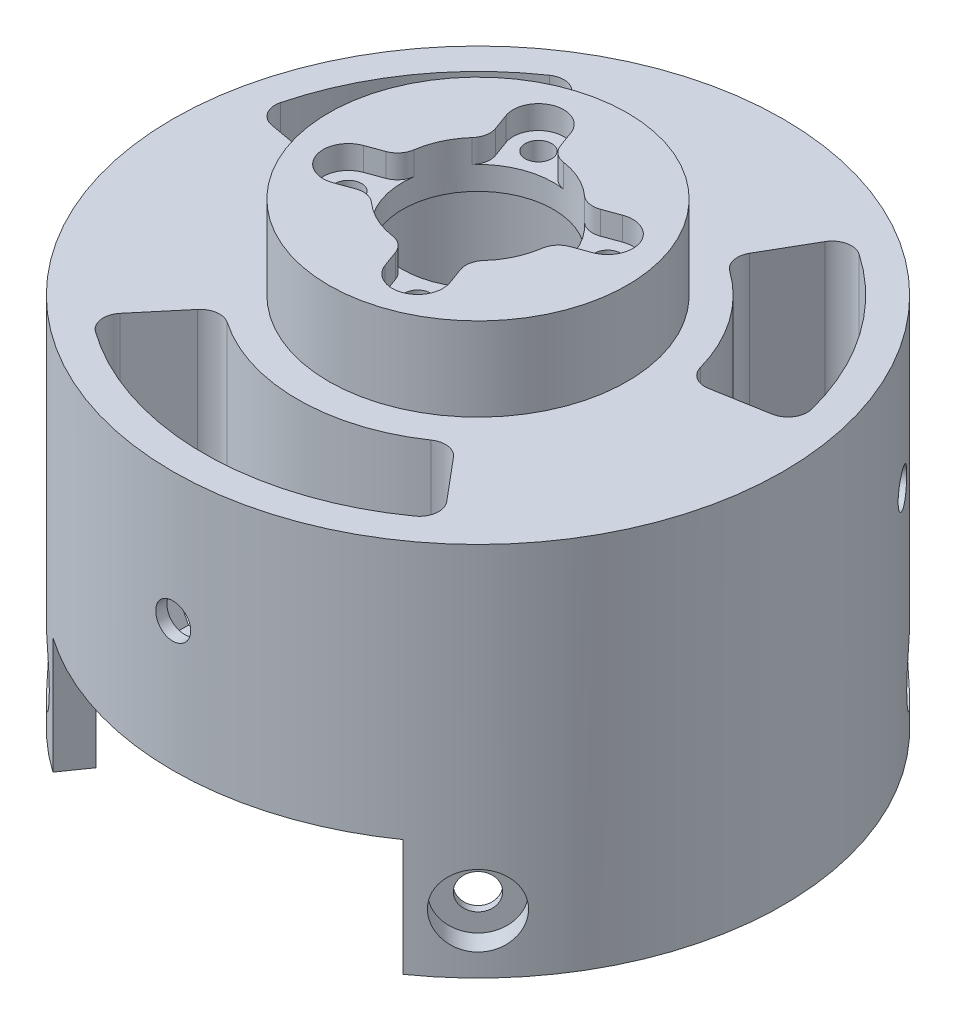
SolidWorks part; units mm, degrees
material "PLA - 3D Printed"
ref_plane "Front Plane" through (0, 0, 0) normal (0, 0, 1) x (1, 0, 0)
ref_plane "Top Plane" through (0, 0, 0) normal (0, 1, 0) x (1, 0, 0)
ref_plane "Right Plane" through (0, 0, 0) normal (1, 0, 0) x (0, 0, -1)
sketch "Sketch1" plane through (0, 0, 0) normal (0, 1, 0) x (1, 0, 0)
  line L0 (-29.85, 23.9174) -> (-29.85, -23.9174)
  line L1 (29.85, 23.9174) -> (29.85, -23.9174)
  line L2 (-29.85, 0) -> (29.85, 0) construction
  arc A0 (-29.85, -23.9174) -> (29.85, -23.9174) centre (0, 0) ccw
  arc A1 (29.85, 23.9174) -> (-29.85, 23.9174) centre (0, 0) ccw
  point P9 (0, 0)
  dimension "D1" = 59.7
  dimension "D2" = 76.5
extrude "Boss-Extrude1" add sketch "Sketch1" along normal blind 44
sketch "Sketch2" plane through (0, 44, 0) normal (0, 1, 0) x (1, 0, 0)
  line L0 (-4.4463, 12.216) -> (0, 0) construction
  line L1 (0, 13) -> (0, 0) construction
  circle A0 centre (0, 0) radius 13
  point P3 (-4.4463, 12.216)
  dimension "D1" = 26
  dimension "D2" = 20
hole_wizard "CBORE for M3 SHCS1" positions "Sketch2" profile "Sketch3" counterbore size "M3" standard "ANSI Metric" end condition through all
sketch "Sketch3" plane through (-4.4463, 44, -12.216) normal (1, 0, 0) x (0, 0, 1)
  line L0 (0, 0) -> (0, 44)
  line L1 (0, 44) -> (1.7, 44)
  line L3 (1.7, 44) -> (1.7, 3)
  line L4 (1.7, 3) -> (3.25, 3)
  line L5 (3.25, 3) -> (3.25, 0)
  line L7 (3.25, 0) -> (0, 0)
  line L11 (0, -6.35) -> (0, 107.95) construction
  dimension "Thru Hole Dia." = 3.4
  dimension "Thru Hole Depth" = 44
  dimension "C'Bore Dia." = 6.5
  dimension "C'Bore Depth" = 3
ref_axis "Axis1" through (0, 44, 0) along (0, -1, 0)
pattern_circular "CirPattern1" count 4 over 360 about axis through (0, 44, 0) along (0, -1, 0) of "CBORE for M3 SHCS1"
sketch "Sketch4" plane through (0, 0, 0) normal (0, -1, 0) x (1, 0, 0)
  circle A0 centre (0, 0) radius 16.2
  dimension "D1" = 32.4
extrude "Cut-Extrude1" cut sketch "Sketch4" against normal blind 38
sketch "Sketch5" plane through (0, 44, 0) normal (0, 1, 0) x (1, 0, 0)
  circle A0 centre (0, 0) radius 9.7
extrude "Cut-Extrude2" cut sketch "Sketch5" against normal through all
ref_plane "Plane1" through (0, 0, -38.25) normal (0, 0, -1) x (-1, 0, 0)
sketch "Sketch7" plane through (0, 0, 0) normal (0, -1, 0) x (1, 0, 0)
  line L5 (29.85, 23.9174) -> (29.85, -23.9174)
  line L6 (-29.85, 23.9174) -> (-29.85, -23.9174)
  arc A0 (-29.85, -23.9174) -> (29.85, -23.9174) centre (0, 0) ccw construction
  arc A1 (29.85, 23.9174) -> (-29.85, 23.9174) centre (0, 0) ccw construction
  arc A2 (-29.85, -23.9174) -> (29.85, -23.9174) centre (0, 0) ccw
  arc A3 (29.85, 23.9174) -> (-29.85, 23.9174) centre (0, 0) ccw
  circle A4 centre (0, 0) radius 42.1622
  dimension "D1" = 84.3245
extrude "Boss-Extrude2" add sketch "Sketch7" against normal up to surface (44 mm away) up to face at (0, 44, 9.7)
sketch "Sketch9" plane through (0, 0, 0) normal (1, 0, 0) x (0, 0, -1)
  line L0 (-42.1622, 0) -> (-38.3127, 44)
  line L1 (-38.3127, 44) -> (-42.1622, 44)
  line L2 (-42.1622, 44) -> (-42.1622, 0) construction
  line L3 (-42.1622, 44) -> (-42.1622, 0)
  line L4 (0, 0) -> (0, 44) construction
  line L5 (42.1622, 44) -> (-42.1622, 44) construction
  dimension "D1" = 5
revolve "Cut-Revolve2" cut sketch "Sketch9" angle 360 about L4
sketch "Sketch10" plane through (0, 0, 0) normal (1, 0, 0) x (0, 0, -1)
  line L0 (-19.2, 44) -> (-19.2, 33.2871)
  line L1 (38.3127, 44) -> (-38.3127, 44) construction
  line L2 (-19.2, 33.2871) -> (-39.25, 33.2871)
  line L3 (-38.3127, 44) -> (-42.1622, 0) construction
  line L4 (-39.25, 33.2871) -> (-38.3127, 44)
  line L5 (-38.3127, 44) -> (-19.2, 44)
  line L6 (0, 0) -> (0, 44) construction
  line L10 (-42.1622, 0) -> (42.1622, 0) construction
  line L11 (-16.2, 0) -> (16.2, 0) construction
  line L12 (-16.2, 0) -> (16.2, 0) construction
  line L13 (38.3127, 44) -> (-38.3127, 44) construction
  dimension "D1" = 10.7129
  dimension "D2" = 33.2871
  dimension "D3" = 3
revolve "Cut-Revolve3" cut sketch "Sketch10" angle 360 about L6
sketch "Sketch13" plane through (0, 33.2871, 0) normal (0, 1, 0) x (1, 0, 0)
  line L0 (0, -35.25) -> (0, -39.25) construction
  circle A0 centre (0, 0) radius 35.25
  circle A1 centre (0, 0) radius 19.2 construction
  circle A2 centre (0, 0) radius 19.2
  circle A3 centre (0, 0) radius 39.25 construction
  dimension "D1" = 4
extrude "Cut-Extrude3" cut sketch "Sketch13" against normal through all both and the other way through all
sketch "Sketch16" plane through (0, 0, 0) normal (0, -1, 0) x (1, 0, 0)
  line L0 (0, -35.25) -> (0, -19.2) construction
  line L1 (-17.625, -30.5274) -> (-9.6, -16.6277)
  line L2 (17.625, -30.5274) -> (9.6, -16.6277)
  line L3 (-34.7145, -6.1211) -> (-18.9083, -3.334)
  line L4 (-22.6583, 27.0031) -> (-12.3415, 14.7081)
  line L5 (22.6583, 27.0031) -> (12.3415, 14.7081)
  line L6 (34.7145, -6.1211) -> (18.9083, -3.334)
  line L7 (0, 0) -> (-33.1242, 12.0562) construction
  circle A1 centre (0, 0) radius 35.25 construction
  circle A2 centre (0, 0) radius 19.2 construction
  arc A3 (-9.6, -16.6277) -> (9.6, -16.6277) centre (0, 0) ccw
  arc A4 (-17.625, -30.5274) -> (17.625, -30.5274) centre (0, 0) ccw
  arc A5 (-22.6583, 27.0031) -> (-34.7145, -6.1211) centre (0, 0) ccw
  arc A6 (-12.3415, 14.7081) -> (-18.9083, -3.334) centre (0, 0) ccw
  arc A7 (22.6583, 27.0031) -> (34.7145, -6.1211) centre (0, 0) cw
  arc A8 (12.3415, 14.7081) -> (18.9083, -3.334) centre (0, 0) cw
  point P19 (0, 0)
  dimension "D1" = 16.05
  dimension "D3" = 60
  dimension "D4" = 110
  dimension "D2" = 2
extrude "Boss-Extrude4" add sketch "Sketch16" against normal up to surface (33.2871 mm away) up to face at (0, 33.2871, 35.25)
sketch "Sketch17" plane through (0, 33.2871, 0) normal (0, 1, 0) x (1, 0, 0)
  line L0 (0, -19.2) -> (0, -23.2) construction
  circle A0 centre (0, 0) radius 23.2
  circle A1 centre (0, 0) radius 19.2 construction
  circle A2 centre (0, 0) radius 19.2
  dimension "D1" = 4
extrude "Boss-Extrude5" add sketch "Sketch17" against normal up to surface (33.2871 mm away) up to face at (-21.2567, 0, -14.8841)
fillet "Fillet2" radius 2.5 12 edges at (-14.9127, 16.6435, 17.7722) (-22.6583, 16.6435, 27.0031) (22.6583, 16.6435, 27.0031) (14.9127, 16.6435, 17.7722) (-17.625, 16.6435, -30.5274) (-34.7145, 16.6435, -6.1211) (-22.8475, 16.6435, -4.0286) (-11.6, 16.6435, -20.0918) (34.7145, 16.6435, -6.1211) (17.625, 16.6435, -30.5274) (11.6, 16.6435, -20.0918) (22.8475, 16.6435, -4.0286)
ref_plane "Plane2" through (0, 16.6435, 0) normal (0, -1, 0) x (-1, 0, 0)
sketch "Sketch18" plane through (0, 16.6435, 0) normal (0, -1, 0) x (-1, 0, 0)
  line L0 (0, 0) -> (28.8751, 20.2186) construction
  line L1 (0, 0) -> (-28.8751, 20.2186) construction
  line L2 (0, 0) -> (0, -35.25) construction
  line L3 (0, 0) -> (-10.7822, -33.5605) construction
  line L4 (0, 0) -> (10.7822, -33.5605) construction
  arc A0 (34.1459, 8.7532) -> (19.9039, 29.0929) centre (0, 0) ccw construction
  arc A1 (-19.9039, 29.0929) -> (-34.1459, 8.7532) centre (0, 0) ccw construction
  arc A2 (-20.5308, -28.6539) -> (20.5308, -28.6539) centre (0, 0) ccw construction
  arc A3 (-20.5308, -28.6539) -> (0, -35.25) centre (0, 0) ccw construction
  arc A4 (0, -35.25) -> (20.5308, -28.6539) centre (0, 0) ccw construction
ref_plane "Plane4" through (-28.8751, 16.6435, -20.2186) normal (-0.8192, 0, -0.5736) x (-0.5736, 0, 0.8192)
sketch "Sketch20" plane through (-28.8751, 16.6435, -20.2186) normal (-0.8192, 0, -0.5736) x (-0.5736, 0, 0.8192)
  circle A0 centre (0, 0) radius 2.25
  dimension "D1" = 4.5
extrude "Cut-Extrude5" cut sketch "Sketch20" against normal blind 10 and the other way through all
sketch "Sketch21" plane through (-28.8751, 16.6435, -20.2186) normal (-0.8192, 0, -0.5736) x (-0.5736, 0, 0.8192)
  line L1 (4.0415, 0) -> (2.0207, 3.5)
  line L2 (2.0207, 3.5) -> (-2.0207, 3.5)
  line L3 (-2.0207, 3.5) -> (-4.0415, 0)
  line L4 (-4.0415, 0) -> (-2.0207, -3.5)
  line L5 (-2.0207, -3.5) -> (2.0207, -3.5)
  line L6 (2.0207, -3.5) -> (4.0415, 0)
  circle A0 centre (0, 0) radius 3.5 construction
  dimension "D1" = 4.0415
  dimension "D2" = 7
extrude "Cut-Extrude6" cut sketch "Sketch21" against normal blind 10 and the other way blind 2.5
pattern_circular "CirPattern2" count 3 over 250 about axis through (0, 0, 0) along (0, 1, 0) of "Cut-Extrude5", "Cut-Extrude6"
sketch "Sketch22" plane through (0, 44, 0) normal (0, 1, 0) x (1, 0, 0)
  line L2 (-12.216, -4.4463) -> (12.216, 4.4463) construction
  line L3 (-13.3276, -1.3923) -> (11.1044, 7.5003) construction
  line L4 (-11.1044, -7.5003) -> (13.3276, 1.3923) construction
  line L5 (-4.4463, 12.216) -> (4.4463, -12.216) construction
  line L6 (-1.3923, 13.3276) -> (7.5003, -11.1044) construction
  line L7 (-7.5003, 11.1044) -> (1.3923, -13.3276) construction
  line L8 (-11.1044, -7.5003) -> (-1.9424, -4.1656)
  line L9 (-1.9424, -4.1656) -> (1.3923, -13.3276)
  line L10 (7.5003, -11.1044) -> (4.1656, -1.9424)
  line L11 (4.1656, -1.9424) -> (13.3276, 1.3923)
  line L12 (11.1044, 7.5003) -> (1.9424, 4.1656)
  line L13 (1.9424, 4.1656) -> (-1.3923, 13.3276)
  line L14 (-7.5003, 11.1044) -> (-4.1656, 1.9424)
  line L15 (-4.1656, 1.9424) -> (-13.3276, -1.3923)
  arc A0 (-13.3276, -1.3923) -> (-11.1044, -7.5003) centre (-12.216, -4.4463) ccw
  arc A1 (1.3923, -13.3276) -> (7.5003, -11.1044) centre (4.4463, -12.216) ccw
  arc A2 (13.3276, 1.3923) -> (11.1044, 7.5003) centre (12.216, 4.4463) ccw
  arc A3 (-1.3923, 13.3276) -> (-7.5003, 11.1044) centre (-4.4463, 12.216) ccw
  arc A10 (-13.3276, -1.3923) -> (-11.1044, -7.5003) centre (-12.216, -4.4463) ccw construction
  arc A11 (13.3276, 1.3923) -> (11.1044, 7.5003) centre (12.216, 4.4463) ccw construction
  circle A12 centre (12.216, 4.4463) radius 3.25 construction
  arc A13 (-1.3923, 13.3276) -> (-7.5003, 11.1044) centre (-4.4463, 12.216) ccw construction
  arc A14 (1.3923, -13.3276) -> (7.5003, -11.1044) centre (4.4463, -12.216) ccw construction
  circle A15 centre (4.4463, -12.216) radius 3.25 construction
  point P2 (0, 0)
  point P11 (0, 0)
extrude "temporary_probnably" cut sketch "Sketch22" against normal up to surface (3 mm away) up to face at (-4.4463, 41, -10.516)
fillet "also_probably_temporary" radius 2.5 8 edges at (-9.6997, 42.5, 0.0718) (-7.4766, 42.5, 6.1798) (0.0718, 42.5, 9.6997) (6.1798, 42.5, 7.4766) (9.6997, 42.5, -0.0718) (7.4766, 42.5, -6.1798) (-0.0718, 42.5, -9.6997) (-6.1798, 42.5, -7.4766)
sketch "Sketch24" plane through (0, 0, 0) normal (1, 0, 0) x (0, 0, -1)
  line L0 (39.25, 33.2871) -> (-39.25, 33.2871) construction
  line L1 (-42.1622, 0) -> (42.1622, 0) construction
  line L2 (39.25, 33.2871) -> (-39.25, 33.2871) construction
  line L3 (-42.1622, 0) -> (42.1622, 0) construction
  line L4 (42.1622, 0) -> (44.1622, 0)
  line L5 (39.25, 33.2871) -> (41.25, 33.2871)
  line L6 (39.25, 33.2871) -> (42.1622, 0)
  line L7 (41.25, 33.2871) -> (44.1622, 0)
  line L8 (0, 33.2871) -> (0, 0) construction
  dimension "D1" = 2
revolve "key_1" [suppressed] add sketch "Sketch24" angle 9 about L8 other way angle 9
fillet "key_2" [suppressed] radius 0.5
sketch "Sketch25" plane through (0, 0, 0) normal (0, -1, 0) x (1, 0, 0)
  line L0 (-22.5129, -32.1517) -> (22.5129, 32.1517) construction
  line L1 (22.5129, -32.1517) -> (-22.5129, 32.1517) construction
  line L2 (-20.2186, 28.8751) -> (-22.5129, 32.1517)
  line L3 (-20.2186, -28.8751) -> (-22.5129, -32.1517)
  line L4 (0, 0) -> (0, 39.25) construction
  line L6 (20.2186, 28.8751) -> (22.5129, 32.1517)
  line L7 (20.2186, -28.8751) -> (22.5129, -32.1517)
  arc A1 (-22.5129, 32.1517) -> (-22.5129, -32.1517) centre (0, 0) ccw
  circle A3 centre (0, 0) radius 35.25 construction
  circle A4 centre (0, 0) radius 39.25 construction
  arc A7 (-20.2186, -28.8751) -> (-20.2186, 28.8751) centre (0, 0) cw
  arc A21 (20.2186, -28.8751) -> (20.2186, 28.8751) centre (0, 0) ccw
  arc A22 (22.5129, 32.1517) -> (22.5129, -32.1517) centre (0, 0) cw
  circle A24 centre (0, 0) radius 39.25 construction
  point P14 (0, 35.25)
  point P16 (0, 35.25)
  dimension "D1" = 70
  dimension "D2" = 4
extrude "Boss-Extrude6" add sketch "Sketch25" along normal blind 15
ref_plane "Plane5" through (0, -7.5, 0) normal (0, -1, 0) x (-1, 0, 0)
sketch "Sketch26" plane through (0, -7.5, 0) normal (0, -1, 0) x (-1, 0, 0)
  line L0 (0, 0) -> (39.25, 0) construction
  line L1 (0, 0) -> (27.7539, -27.7539) construction
  arc A0 (22.5129, -32.1517) -> (22.5129, 32.1517) centre (0, 0) ccw construction
  dimension "D1" = 45
ref_plane "Plane6" through (-27.7539, -7.5, 27.7539) normal (-0.7071, 0, 0.7071) x (0.7071, 0, 0.7071)
sketch "Sketch28" plane through (-27.7539, -7.5, 27.7539) normal (-0.7071, 0, 0.7071) x (0.7071, 0, 0.7071)
  circle A0 centre (0, 0) radius 2.25
  dimension "D1" = 4.5
extrude "Cut-Extrude7" cut sketch "Sketch28" along normal through all and the other way up to surface other way up to face at (0, 6.9861, -1.1089)
sketch "Sketch29" plane through (-27.7539, -7.5, 27.7539) normal (-0.7071, 0, 0.7071) x (0.7071, 0, 0.7071)
  circle A0 centre (0, 0) radius 2.25 construction
  circle A1 centre (0, 0) radius 2.25
  circle A2 centre (0, 0) radius 4.6
  dimension "D1" = 9.2
extrude "Cut-Extrude8" cut sketch "Sketch29" against normal blind 3
mirror "Mirror1" about plane through (0, 0, 0) normal (0, 0, 1) of "Cut-Extrude8", "Cut-Extrude7"
mirror "Mirror2" about plane through (0, 0, 0) normal (1, 0, 0) of "Mirror1"
sketch "Sketch31" plane through (0, 33.2871, 0) normal (0, 1, 0) x (1, 0, 0)
  circle A1 centre (0, 0) radius 39.25
  circle A2 centre (0, 0) radius 39.25
  dimension "D1" = 0
extrude "Cut-Extrude9" cut sketch "Sketch31" against normal through all flip side to cut
